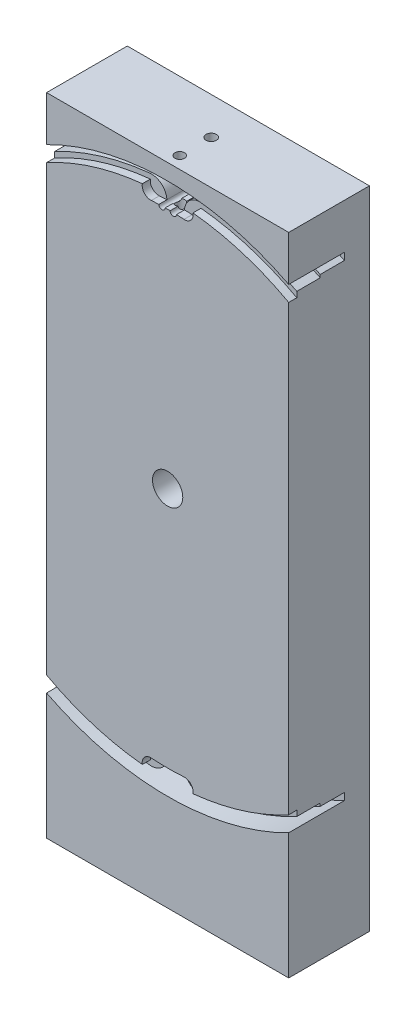
SolidWorks part; units mm, degrees
ref_plane "Front Plane" through (0, 0, 0) normal (0, 0, 1) x (1, 0, 0)
ref_plane "Top Plane" through (0, 0, 0) normal (0, 1, 0) x (1, 0, 0)
ref_plane "Right Plane" through (0, 0, 0) normal (1, 0, 0) x (0, 0, -1)
sketch "Sketch1" plane through (0, 0, 0) normal (0, 0, 1) x (1, 0, 0)
  line L0 (-38.1, 101.6) -> (38.1, -101.6) construction
  line L1 (-38.1, 101.6) -> (38.1, 101.6)
  line L2 (-38.1, 101.6) -> (-38.1, -101.6)
  line L3 (-38.1, -101.6) -> (38.1, -101.6)
  line L4 (38.1, 101.6) -> (38.1, -101.6)
  circle A0 centre (0, 12.7) radius 4.7625
  point P6 (0, 0)
  point P7 (0, 101.6)
  dimension "D4" = 9.525
  dimension "D1" = 76.2
  dimension "D2" = 203.2
  dimension "D3" = 88.9
extrude "Boss-Extrude1" add sketch "Sketch1" along normal blind 25.4
sketch "Sketch3" plane through (0, 0, 25.4) normal (0, 0, 1) x (1, 0, 0)
  circle A0 centre (0, 12.7) radius 83.82 construction
  circle A1 centre (0, 12.7) radius 83.82 construction
  circle A2 centre (0, 12.7) radius 81.9404 construction
  circle A3 centre (0, 12.7) radius 81.9404 construction
  circle A4 centre (0, 12.7) radius 83.8708
  circle A6 centre (0, 12.7) radius 81.8896
  dimension "D1" = 0.0508
  dimension "D3" = 0.0508
extrude "Cut-Extrude2" cut sketch "Sketch3" against normal up to surface (17.526 mm away)
sketch "Sketch4" plane through (0, 0, 25.4) normal (0, 0, 1) x (1, 0, 0)
  line L0 (65.841, 60.0988) -> (66.8082, 60.929) construction
  line L1 (-66.8717, 60.8408) -> (-65.841, 60.0988) construction
  line L2 (-66.8717, 60.8408) -> (-68.4976, 58.5824)
  line L3 (-66.9426, 60.8292) -> (-65.8295, 60.0279)
  line L4 (65.8321, 60.0242) -> (66.8767, 60.9208)
  line L5 (-58.1196, 12.7) -> (58.1196, 12.7) construction
  line L6 (-66.8717, -35.4408) -> (-65.841, -34.6988) construction
  line L7 (65.841, -34.6988) -> (66.8082, -35.529) construction
  line L8 (65.8321, -34.6242) -> (66.8767, -35.5208)
  line L9 (-66.9426, -35.4292) -> (-65.8295, -34.6279)
  line L10 (-66.8717, -35.4408) -> (-68.4976, -33.1824)
  arc A0 (8.128, 93.4194) -> (2.7181, 88.8515) centre (7.6343, 88.5166) ccw construction
  arc A1 (65.841, 60.0988) -> (8.128, 93.4194) centre (0, 12.7) ccw construction
  arc A2 (-8.128, 93.4194) -> (-65.841, 60.0988) centre (0, 12.7) ccw construction
  arc A3 (-2.7181, 88.8515) -> (-8.128, 93.4194) centre (-7.6343, 88.5166) ccw construction
  arc A4 (2.7181, 88.8515) -> (-2.7181, 88.8515) centre (0, 12.7) ccw construction
  arc A6 (-8.1229, 93.3689) -> (-65.8295, 60.0279) centre (0, 12.7) ccw
  arc A7 (-2.7657, 88.799) -> (-8.1229, 93.3689) centre (-7.6343, 88.5166) ccw
  arc A8 (2.7657, 88.799) -> (-2.7657, 88.799) centre (0, 12.7) ccw
  arc A9 (8.1229, 93.3689) -> (2.7657, 88.799) centre (7.6343, 88.5166) ccw
  arc A10 (8.128, 93.4194) -> (2.7181, 88.8515) centre (7.6343, 88.5166) ccw construction
  arc A11 (65.841, 60.0988) -> (8.128, 93.4194) centre (0, 12.7) ccw construction
  arc A12 (-8.128, 93.4194) -> (-65.841, 60.0988) centre (0, 12.7) ccw construction
  arc A13 (-2.7181, 88.8515) -> (-8.128, 93.4194) centre (-7.6343, 88.5166) ccw construction
  arc A14 (2.7181, 88.8515) -> (-2.7181, 88.8515) centre (0, 12.7) ccw construction
  arc A15 (66.8082, 60.929) -> (-66.8717, 60.8408) centre (0, 12.7) ccw construction
  circle A16 centre (0, 12.7) radius 4.7625 construction
  arc A17 (65.8321, 60.0242) -> (8.1229, 93.3689) centre (0, 12.7) ccw
  arc A18 (66.8767, 60.9208) -> (-66.9426, 60.8292) centre (0, 12.7) ccw
  circle A19 centre (0, 12.7) radius 4.7625 construction
  circle A20 centre (0, 12.7) radius 4.7625 construction
  arc A21 (66.8082, -35.529) -> (-66.8717, -35.4408) centre (0, 12.7) cw construction
  arc A22 (2.7181, -63.4515) -> (-2.7181, -63.4515) centre (0, 12.7) cw construction
  arc A23 (-2.7181, -63.4515) -> (-8.128, -68.0194) centre (-7.6343, -63.1166) cw construction
  arc A24 (-8.128, -68.0194) -> (-65.841, -34.6988) centre (0, 12.7) cw construction
  arc A25 (65.841, -34.6988) -> (8.128, -68.0194) centre (0, 12.7) cw construction
  arc A26 (8.128, -68.0194) -> (2.7181, -63.4515) centre (7.6343, -63.1166) cw construction
  arc A27 (66.8767, -35.5208) -> (-66.9426, -35.4292) centre (0, 12.7) cw
  arc A28 (65.8321, -34.6242) -> (8.1229, -67.9689) centre (0, 12.7) cw
  arc A29 (8.1229, -67.9689) -> (2.7657, -63.399) centre (7.6343, -63.1166) cw
  arc A30 (2.7657, -63.399) -> (-2.7657, -63.399) centre (0, 12.7) cw
  arc A31 (-2.7657, -63.399) -> (-8.1229, -67.9689) centre (-7.6343, -63.1166) cw
  arc A32 (-8.1229, -67.9689) -> (-65.8295, -34.6279) centre (0, 12.7) cw
  point P17 (0, 12.7)
  dimension "D1" = 1.27
  dimension "D2" = 0.0508
extrude "Cut-Extrude3" cut sketch "Sketch4" against normal up to surface (9.906 mm away) contours A28 A29 A30 A31 A32 L9 A27 L8 | A17 A9 A8 A7 A6 L3 A18 L4
sketch "Sketch5" plane through (0, 0, 25.4) normal (0, 0, 1) x (1, 0, 0)
  line L0 (-44.0388, 78.936) -> (-44.134, 80.7121)
  line L1 (24.4478, 12.7) -> (-24.4478, 12.7) construction
  line L2 (0, 40.3177) -> (0, -14.9177) construction
  line L3 (44.0388, 78.936) -> (44.134, 80.7121)
  line L4 (44.0388, -53.536) -> (44.134, -55.3121)
  line L5 (-44.0388, -53.536) -> (-44.134, -55.3121)
  arc A0 (2.7657, 88.799) -> (-2.7657, 88.799) centre (0, 12.7) ccw construction
  arc A1 (2.7657, 88.799) -> (-2.7657, 88.799) centre (0, 12.7) ccw construction
  arc A2 (-7.969, 91.8399) -> (-64.5527, 59.1713) centre (0, 12.7) ccw construction
  arc A3 (-7.969, 91.8399) -> (-44.0388, 78.936) centre (0, 12.7) ccw
  arc A4 (-2.7657, 88.799) -> (-8.1229, 93.3689) centre (-7.6343, 88.5166) ccw construction
  arc A5 (-2.7657, 88.799) -> (-5.147, 88.6751) centre (0, 12.7) ccw
  arc A6 (-8.1229, 93.3689) -> (-38.1, 84.267) centre (0, 12.7) ccw construction
  arc A7 (-2.7657, 88.799) -> (-8.1229, 93.3689) centre (-7.6343, 88.5166) ccw
  arc A8 (-5.147, 88.6751) -> (-7.969, 91.8399) centre (-5.3284, 91.3538) cw
  arc A9 (8.1229, 93.3689) -> (44.134, 80.7121) centre (0, 12.7) cw
  arc A10 (-8.1229, 93.3689) -> (-44.134, 80.7121) centre (0, 12.7) ccw
  arc A11 (5.147, 88.6751) -> (7.969, 91.8399) centre (5.3284, 91.3538) ccw
  circle A12 centre (0, 12.7) radius 4.7625 construction
  circle A13 centre (0, 12.7) radius 4.7625 construction
  arc A14 (2.7657, 88.799) -> (8.1229, 93.3689) centre (7.6343, 88.5166) cw
  arc A15 (2.7657, 88.799) -> (5.147, 88.6751) centre (0, 12.7) cw
  arc A16 (7.969, 91.8399) -> (44.0388, 78.936) centre (0, 12.7) cw
  arc A17 (2.7657, -63.399) -> (-2.7657, -63.399) centre (0, 12.7) cw construction
  arc A18 (7.969, -66.4399) -> (44.0388, -53.536) centre (0, 12.7) ccw
  arc A19 (2.7657, -63.399) -> (5.147, -63.2751) centre (0, 12.7) ccw
  arc A20 (2.7657, -63.399) -> (8.1229, -67.9689) centre (7.6343, -63.1166) ccw
  arc A21 (5.147, -63.2751) -> (7.969, -66.4399) centre (5.3284, -65.9538) cw
  arc A22 (-8.1229, -67.9689) -> (-44.134, -55.3121) centre (0, 12.7) cw
  arc A23 (8.1229, -67.9689) -> (44.134, -55.3121) centre (0, 12.7) ccw
  arc A24 (-5.147, -63.2751) -> (-7.969, -66.4399) centre (-5.3284, -65.9538) ccw
  arc A25 (-2.7657, -63.399) -> (-8.1229, -67.9689) centre (-7.6343, -63.1166) cw
  arc A26 (-2.7657, -63.399) -> (-5.147, -63.2751) centre (0, 12.7) cw
  arc A27 (-7.969, -66.4399) -> (-44.0388, -53.536) centre (0, 12.7) cw
  point P11 (0, 12.7)
  point P12 (0, 12.7)
  dimension "D1" = 2.3813
extrude "Cut-Extrude4" cut sketch "Sketch5" against normal blind 2.54
sketch "Sketch7" plane through (0, 101.6, 0) normal (0, 1, 0) x (1, 0, 0)
  circle A0 centre (0, -11.684) radius 1.6319 construction
  circle A1 centre (0, -11.684) radius 1.6319
  circle A2 centre (0, -21.59) radius 1.524 construction
  circle A3 centre (0, -21.59) radius 1.524
extrude "Cut-Extrude5" cut sketch "Sketch7" against normal blind 17.78
sketch "Sketch8" plane through (0, 0, 15.494) normal (0, 0, 1) x (1, 0, 0)
  line L3 (0, 88.8492) -> (0, 85.1559) construction
  arc A0 (2.7657, 88.799) -> (-2.7657, 88.799) centre (0, 12.7) ccw construction
  arc A1 (2.7657, 88.799) -> (-2.7657, 88.799) centre (0, 12.7) ccw construction
  circle A2 centre (-1.774, 88.8285) radius 0.9922
  circle A3 centre (1.774, 88.8285) radius 0.9922
  point P5 (0, 0)
  dimension "D1" = 1.9844
extrude "Cut-Extrude6" cut sketch "Sketch8" along normal through all
